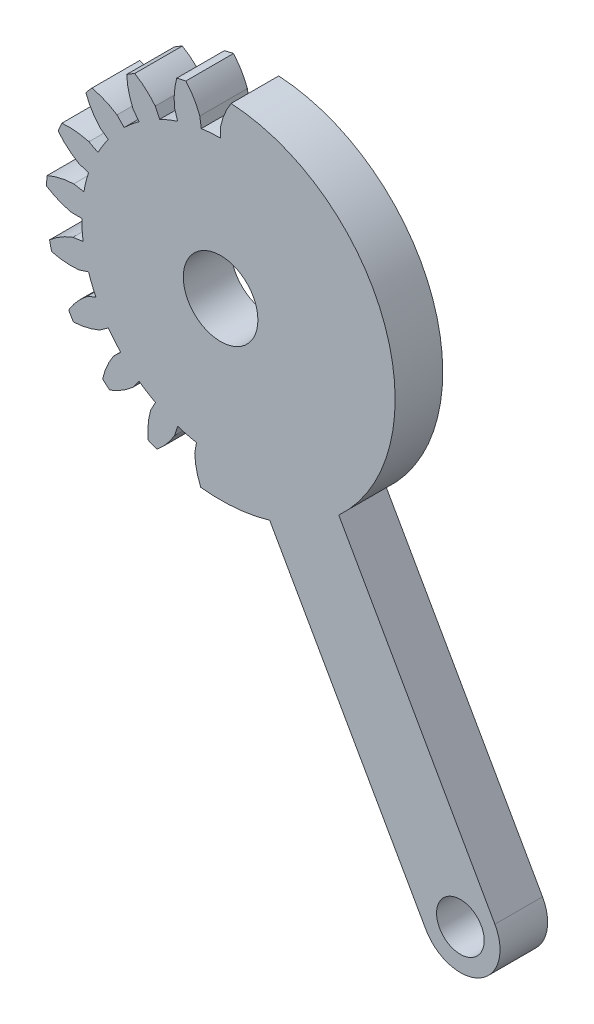
SolidWorks part; units mm, degrees
material "Plastique personnalisé"
ref_plane "Plan de face" through (0, 0, 0) normal (0, 0, 1) x (1, 0, 0)
ref_plane "Plan de dessus" through (0, 0, 0) normal (0, 1, 0) x (1, 0, 0)
ref_plane "Plan de droite" through (0, 0, 0) normal (1, 0, 0) x (0, 0, -1)
ref_axis "Axe2" through (0, 0, 0) along (0, 0, 1)
sketch "Esquisse1" plane through (0, 0, 0) normal (0, 0, 1) x (1, 0, 0)
  circle A3 centre (0, 0) radius 10
  circle A4 centre (0, 0) radius 11
  circle A5 centre (0, 0) radius 8.75
  circle A6 centre (0, 0) radius 9
  circle A7 centre (0, 0) radius 9.3969
  dimension "Pitch circle" = 20
  dimension "Addendum circle" = 22
  dimension "Root circle" = 17.5
  dimension "Clearance circle" = 18
  dimension "Base circle" = 18.7939
sketch "Involute" plane through (0, 0, 0) normal (0, 0, 1) x (1, 0, 0)
  line L0 (0, 0) -> (0, 9.3969)
  line L1 (0, 0) -> (4.6985, 8.138) construction
  line L2 (0, 0) -> (8.138, 4.6985) construction
  line L3 (0, 0) -> (9.3969, 0) construction
  line L4 (9.3969, 0) -> (9.3969, 14.7607) construction
  line L5 (8.138, 4.6985) -> (3.2178, 13.2205) construction
  line L6 (4.6985, 8.138) -> (0.4374, 10.5981) construction
  line L7 (0, 0) -> (3.0902, 9.5106)
  line L8 (0, 0) -> (1.5643, 9.8769) construction
  line L10 (0.8704, 9.962) -> (0, 0) construction
  circle A0 centre (0, 0) radius 9.3969 construction
  circle A1 centre (0, 0) radius 10 construction
  arc A5 (1.5643, 9.8769) -> (0.1723, 9.9985) centre (0, 0) ccw
  spline S0 degree 3 poles (0, 9.3969) (0.8266, 13.2451) (6.2259, 14.7657) (9.3969, 14.7607) knots 0 0 0 0 1 1 1 1
  spline S1 degree 3 poles (1.6297, 9.2545) (1.483, 13.1878) (-3.5708, 15.6216) (-6.6946, 16.1667) knots 0 0 0 0 1 1 1 1
  point P11 (0, 0)
  dimension "D2" = 9.8404
  dimension "D3" = 4.9202
  dimension "Base circle quarter circumference" = 14.7607
  dimension "Circular Pitch" = 18
  dimension "D4" = 90
  dimension "D1" = 4
sketch "Esquisse2" plane through (0, 0, 0) normal (0, 0, 1) x (1, 0, 0)
  line L1 (0, 0) -> (0, 9.3969) construction
  line L2 (0, 8.75) -> (0, 9.3969)
  line L3 (1.6297, 9.2545) -> (1.5175, 8.6174)
  arc A1 (0.6615, 10.9801) -> (0, 9.3969) centre (4.5797, 8.4132) ccw
  circle A2 centre (0, 0) radius 8.75 construction
  circle A3 centre (0, 0) radius 11 construction
  arc A4 (1.5175, 8.6174) -> (0, 8.75) centre (0, 0) ccw
  arc A5 (1.2528, 10.9284) -> (0.6615, 10.9801) centre (0, 0) ccw
  arc A7 (1.6297, 9.2545) -> (1.2503, 10.9287) centre (-3.0193, 9.0811) ccw
  spline S2 degree 3 poles (1.6297, 9.2545) (1.483, 13.1878) (-3.5708, 15.6216) (-6.6946, 16.1667) knots 0 0 0 0 1 1 1 1 construction
  spline S3 degree 3 poles (0, 9.3969) (0.8266, 13.2451) (6.2259, 14.7657) (9.3969, 14.7607) knots 0 0 0 0 1 1 1 1 construction
  point P4 (0.7616, 8.7168)
extrude "Extrusion dents" add sketch "Esquisse2" along normal blind 3 contours L3 A7 A5 A1 L2 A4 region at (0.8468, 9.6943, 0)
pattern_circular "Répétition circulaire2" count 20 over 360 about axis through (0, 0, 0) along (0, 0, 1) of bodies 191
extrude "Extrusion disque" add sketch "Esquisse1" along normal blind 3 contours A5 region at (0, 0, 0)
sketch "Esquisse3" plane through (0, 0, 3) normal (0, 0, 1) x (1, 0, 0)
  circle A2 centre (0, 0) radius 2.35
  dimension "D1" = 4.7
sketch "Esquisse5" plane through (0, 0, 0) normal (0, 0, -1) x (-1, 0, 0)
  line L0 (-0.9571, 10.9583) -> (0.9574, -10.9583)
  line L1 (-1.5179, 10.1093) -> (-0.2576, 10.2191) construction
  line L2 (0, -9.3969) -> (1.6297, -9.2545) construction
  circle A0 centre (0, 0) radius 11 construction
  arc A3 (-1.2503, 10.9287) -> (-1.6297, 9.2545) centre (3.0193, 9.0811) ccw construction
  arc A4 (0, 9.3969) -> (-0.6615, 10.9801) centre (-4.5797, 8.4132) ccw construction
  arc A5 (-0.9571, 10.9583) -> (0.9574, -10.9583) centre (0, 0) ccw
  point P4 (-0.8878, 10.1642)
  point P17 (0.8148, -9.3257)
extrude "Boss.-Extru.1" add sketch "Esquisse5" against normal blind 3
sketch "Esquisse6" plane through (0, 0, 0) normal (0, 0, -1) x (-1, 0, 0)
  line L0 (0, 0) -> (-15.111, -26.7375) construction
  line L1 (1.2503, -10.9287) -> (0, 0) construction
  line L2 (-7.4471, -8.0958) -> (-17.2875, -25.5074)
  line L4 (-3.0941, -10.5559) -> (-12.9345, -27.9675)
  circle A0 centre (0, 0) radius 11 construction
  arc A2 (-17.2875, -25.5074) -> (-12.9345, -27.9675) centre (-15.111, -26.7375) ccw
  circle A3 centre (-15.111, -26.7375) radius 1.5
  arc A4 (-7.4471, -8.0958) -> (-3.0941, -10.5559) centre (0, 0) ccw
  dimension "D4" = 3
  dimension "D1" = 36
  dimension "D2" = 20
  dimension "D3" = 2.5
extrude "Boss.-Extru.2" add sketch "Esquisse6" against normal blind 3
extrude "Enlèv. mat.-Extru.1" cut sketch "Esquisse3" against normal through all contours A2
sketch "Esquisse8" plane through (0, 0, 0) normal (0, 0, 1) x (1, 0, 0)
  circle A2 centre (-1.6378, 5.0406) radius 0.8
  circle A3 centre (-5.3, 0) radius 0.8
  circle A4 centre (-1.6378, -5.0406) radius 0.8
  circle A7 centre (4.2878, 3.1153) radius 0.8
  circle A8 centre (4.2878, -3.1153) radius 0.8
  dimension "D1" = 1.6
  dimension "D2" = 1.6
  dimension "D3" = 1.6
  dimension "D4" = 1.6
  dimension "D5" = 1.6
  dimension "D6" = 4.2878
  dimension "D7" = 3.1153
  dimension "D8" = 4.2878
  dimension "D9" = 3.1153
  dimension "D10" = 1.6378
  dimension "D11" = 5.0406
  dimension "D12" = 5.3
  dimension "D13" = 1.6378
  dimension "D14" = 5.0406
extrude "Fixation palonnier SG90" cut sketch "Esquisse8" along normal blind 2.5
equation "\"Module\"= 1"
equation "\"Nb of teeth\"= 20"
equation "\"Pressure angle\"= 20deg"
equation "\"Pitch circle@Esquisse1\"= \"Module\" * \"Nb of teeth\""
equation "\"Addendum circle@Esquisse1\" = \"Pitch circle@Esquisse1\" + ( \"Module\" * 2 )"
equation "\"Clearance circle@Esquisse1\"= \"Pitch circle@Esquisse1\" - ( \"Module\" * 2 )"
equation "\"Root circle@Esquisse1\"= \"Pitch circle@Esquisse1\" - ( ( \"Module\" * 1.25 ) * 2 )"
equation "\"Base circle@Esquisse1\"= \"Pitch circle@Esquisse1\" * cos ( \"Pressure angle\" )"
equation "\"D2@Involute\" = \"Base circle quarter circumference@Involute\" / 3 * 2"
equation "\"Base circle quarter circumference@Involute\" = \"Base circle@Esquisse1\" * pI / 4"
equation "\"D3@Involute\" = \"Base circle quarter circumference@Involute\" / 3"
equation "\"Circular Pitch@Involute\"=360 / \"Nb of teeth\""
equation "\"D1@Répétition circulaire2\"= \"Nb of teeth\""
equation "\"D1@Extrusion disque\" = \"D1@Extrusion dents\""
